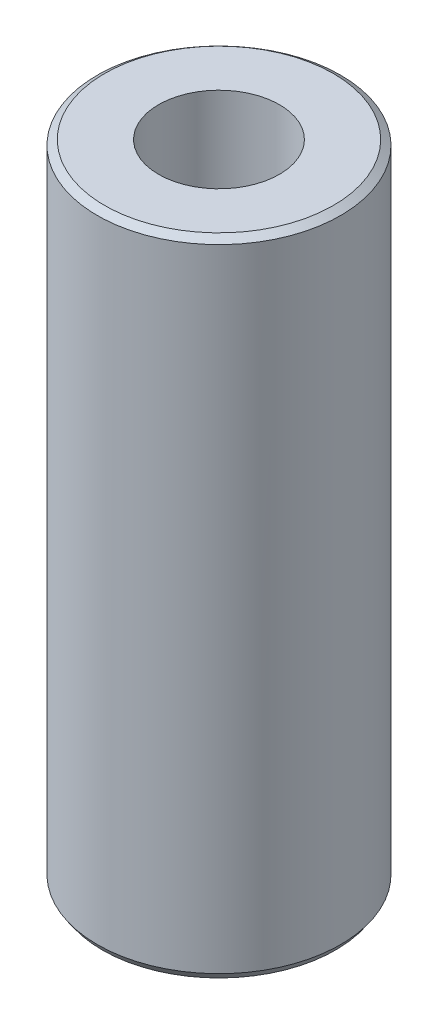
SolidWorks part; units mm, degrees
ref_plane "Front Plane" through (0, 0, 0) normal (0, 0, 1) x (1, 0, 0)
ref_plane "Top Plane" through (0, 0, 0) normal (0, 1, 0) x (1, 0, 0)
ref_plane "Right Plane" through (0, 0, 0) normal (1, 0, 0) x (0, 0, -1)
sketch "Sketch1" plane through (0, 0, 0) normal (0, 1, 0) x (1, 0, 0)
  circle A0 centre (0, 0) radius 5
  dimension "SHAFT_OD" = 10
extrude "Boss-Extrude1" add sketch "Sketch1" along normal blind 26.4578
sketch "Sketch2" plane through (0, 0, 0) normal (0, 1, 0) x (1, 0, 0)
  circle A0 centre (0, 0) radius 2.4833
  dimension "BORE_D" = 4.9667
extrude "Cut-Extrude1" cut sketch "Sketch2" along normal through all
chamfer "Chamfer1" distance 0.2072 angle 55.337 2 edges at (0, 26.4578, 5) (0, 0, 5) first distance on face at (0, 26.4578, 5) first distance on face at (0, 0, 2.4833)
